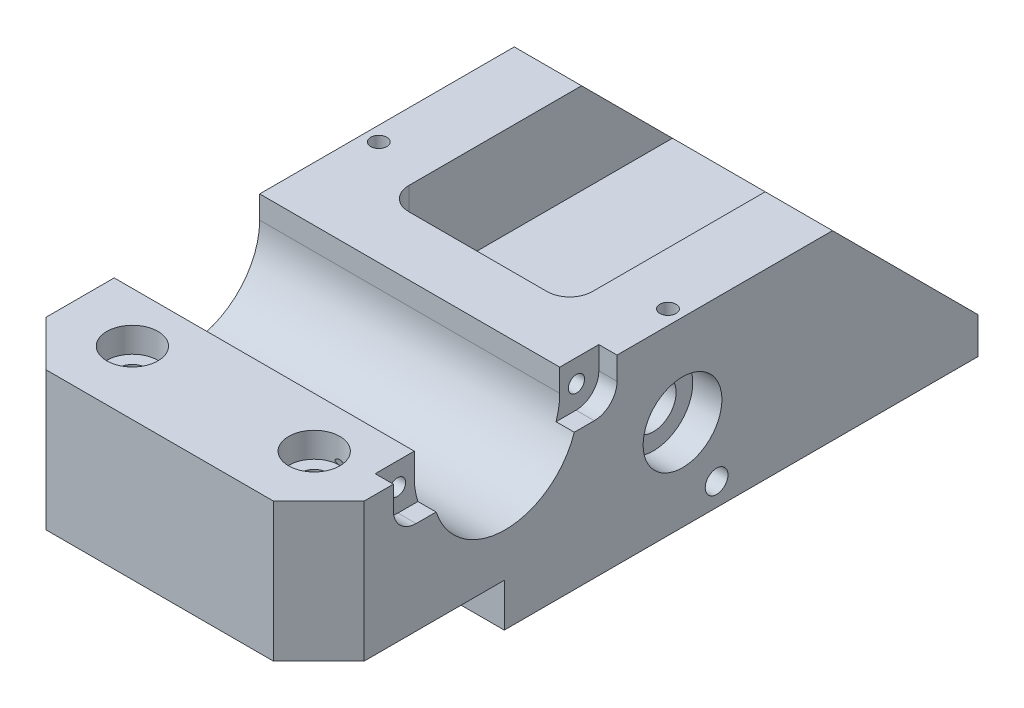
SolidWorks part; units mm, degrees
material "Nylon 6/10"
ref_plane "Front Plane" through (0, 0, 0) normal (0, 0, 1) x (1, 0, 0)
ref_plane "Top Plane" through (0, 0, 0) normal (0, 1, 0) x (1, 0, 0)
ref_plane "Right Plane" through (0, 0, 0) normal (1, 0, 0) x (0, 0, -1)
sketch "Sketch1" plane through (0, 0, 0) normal (0, 1, 0) x (1, 0, 0)
  line L1 (-22.225, -46.0375) -> (22.225, -46.0375)
  line L2 (-22.225, -46.0375) -> (-22.225, 46.0375)
  line L3 (-22.225, 46.0375) -> (22.225, 46.0375)
  line L4 (22.225, -46.0375) -> (22.225, 46.0375)
  line L5 (-22.225, -46.0375) -> (22.225, 46.0375) construction
  line L6 (-22.225, 46.0375) -> (22.225, -46.0375) construction
  point P0 (0, 0)
  dimension "D1" = 44.45
  dimension "D2" = 92.075
extrude "Base" add sketch "Sketch1" along normal blind 12.7 and the other way blind 12.7
sketch "Sketch2" plane through (0, 0, -46.0375) normal (0, 0, -1) x (-1, 0, 0)
  line L1 (-22.225, -12.7) -> (22.225, -12.7) construction
  circle A0 centre (0, -12.7) radius 4.7625
  dimension "D1" = 9.525
extrude "ShaftGuide" cut sketch "Sketch2" against normal blind 41.275
ref_plane "Plane1" through (0, -12.7, 0) normal (0, -1, 0) x (-1, 0, 0)
sketch "Sketch3" plane through (0, -12.7, 0) normal (0, -1, 0) x (-1, 0, 0)
  line L0 (10.922, -20.1295) -> (16.002, -20.1295)
  line L1 (22.225, -46.0375) -> (-22.225, -46.0375) construction
  line L2 (-22.225, -46.0375) -> (-22.225, 46.0375) construction
  line L3 (0, 0) -> (0, 102.0916) construction
  line L5 (-10.922, -20.1295) -> (-10.922, -3.3655)
  line L6 (-22.225, -46.0375) -> (22.225, -46.0375)
  line L7 (-10.922, -3.3655) -> (10.922, -3.3655)
  line L8 (10.922, -20.1295) -> (10.922, -3.3655)
  line L10 (-10.922, -20.1295) -> (-22.225, -20.1295)
  line L11 (-22.225, -46.0375) -> (-22.225, -20.1295)
  line L13 (22.225, -46.0375) -> (22.225, -20.1295)
  line L14 (4.7625, 46.0375) -> (4.7625, 4.7625)
  line L15 (4.7625, 4.7625) -> (-4.7625, 4.7625)
  line L16 (-4.7625, 4.7625) -> (-4.7625, 46.0375)
  line L17 (-4.7625, 46.0375) -> (-22.225, 46.0375)
  line L18 (-22.225, 46.0375) -> (-22.225, -46.0375)
  line L19 (-22.225, -46.0375) -> (22.225, -46.0375)
  line L20 (22.225, -46.0375) -> (22.225, 46.0375)
  line L21 (22.225, 46.0375) -> (4.7625, 46.0375)
  line L23 (22.225, 46.0375) -> (22.225, -46.0375) construction
  line L25 (-4.7625, 46.0375) -> (-22.225, 46.0375) construction
  line L26 (22.225, -20.1295) -> (16.002, -20.1295)
  line L28 (22.225, -46.0375) -> (22.225, 46.0375) construction
  line L29 (22.225, 46.0375) -> (4.7625, 46.0375) construction
  dimension "D6" = 21.844
  dimension "D3" = 49.403
  dimension "D7" = 16.764
  dimension "D1" = 0
extrude "ActuatorPlaneCut" cut sketch "Sketch3" against normal blind 6.0325
sketch "Sketch5" plane through (0, 0, 0) normal (0, 1, 0) x (1, 0, 0)
  line L1 (12.827, 11.1125) -> (-12.827, 11.1125)
  line L2 (12.827, -1.5875) -> (12.827, 11.1125)
  line L3 (12.827, -1.5875) -> (-12.827, -1.5875)
  line L4 (0, 0) -> (0, 121.8983) construction
  line L5 (-10.922, -3.3655) -> (10.922, -3.3655) construction
  line L6 (-12.827, -1.5875) -> (-12.827, 11.1125)
  point P17 (12.827, -1.5875)
  point P20 (12.827, 11.1125)
  dimension "D3" = 1.778
  dimension "D1" = 12.7
  dimension "D2" = 25.654
extrude "CenterSlot" cut sketch "Sketch5" along normal through all and the other way through all
fillet "CenterSlotFillet" radius 3.175 4 edges at (-12.827, 0, -11.1125) (-12.827, 0, 1.5875) (12.827, 0, 1.5875) (12.827, 0, -11.1125)
sketch "Sketch40" plane through (0, -12.7, 0) normal (0, -1, 0) x (1, 0, 0)
  line L1 (10.922, -0.9525) -> (-10.922, -0.9525)
  line L2 (10.922, -0.9525) -> (10.922, 16.9545)
  line L3 (7.747, 20.1295) -> (-7.747, 20.1295)
  line L4 (-10.922, -0.9525) -> (-10.922, 16.9545)
  line L6 (10.922, 3.3655) -> (10.922, 20.1295) construction
  line L7 (-9.652, 1.5875) -> (9.652, 1.5875) construction
  arc A0 (-7.747, 20.1295) -> (-10.922, 16.9545) centre (-7.747, 16.9545) ccw
  arc A1 (7.747, 20.1295) -> (10.922, 16.9545) centre (7.747, 16.9545) cw
  point P8 (-10.922, 20.1295)
  dimension "D1" = 3.175
  dimension "D2" = 2.54
extrude "GearBoxPit" cut sketch "Sketch40" against normal blind 11.176
sketch "Sketch60" plane through (0, 12.7, 0) normal (0, 1, 0) x (1, 0, 0)
  line L0 (22.225, 46.0375) -> (-22.225, 46.0375) construction
  line L1 (-12.827, 7.9375) -> (12.827, 7.9375)
  line L2 (-12.827, 7.9375) -> (-12.827, 46.0375)
  line L3 (-12.827, 46.0375) -> (12.827, 46.0375)
  line L4 (12.827, 7.9375) -> (12.827, 46.0375)
  line L5 (12.827, 1.5875) -> (12.827, 7.9375) construction
extrude "FrontCutaway" cut sketch "Sketch60" against normal blind 12.7
chamfer "ChamferFront" distance 20.32 angle 45 2 edges at (-17.526, 12.7, -46.0375) (17.526, 12.7, -46.0375)
sketch "Sketch67" plane through (0, -12.7, 0) normal (0, -1, 0) x (-1, 0, 0)
  line L0 (-12.3825, -5.3975) -> (12.3825, -5.3975) construction
  line L1 (-12.3825, -5.0006) -> (12.3825, -5.0006)
  line L2 (-12.3825, -5.7944) -> (12.3825, -5.7944)
  line L3 (-12.3825, -16.0655) -> (12.3825, -16.0655) construction
  line L4 (-12.3825, -15.6686) -> (12.3825, -15.6686)
  line L5 (-12.3825, -16.4624) -> (12.3825, -16.4624)
  line L6 (9.652, -1.5875) -> (-9.652, -1.5875) construction
  line L7 (0, 0.0055) -> (0, 0.7987) construction
  arc A0 (-12.3825, -5.0006) -> (-12.3825, -5.7944) centre (-12.3825, -5.3975) ccw
  arc A1 (12.3825, -5.7944) -> (12.3825, -5.0006) centre (12.3825, -5.3975) ccw
  arc A2 (-12.3825, -15.6686) -> (-12.3825, -16.4624) centre (-12.3825, -16.0655) ccw
  arc A3 (12.3825, -16.4624) -> (12.3825, -15.6686) centre (12.3825, -16.0655) ccw
  point P2 (0, -5.3975)
  point P9 (0, -16.0655)
  dimension "D1" = 0.7937
  dimension "D2" = 3.81
  dimension "D3" = 24.765
  dimension "D4" = 10.668
extrude "GearBoxSlotsH" cut sketch "Sketch67" against normal blind 2.286
sketch "Sketch55" plane through (-22.225, 0, 0) normal (-1, 0, 0) x (0, 0, 1)
  line L0 (-46.0375, -12.7) -> (20.1295, -12.7) construction
  line L1 (-11.1125, -12.7) -> (-11.1125, -7.9375) construction
  circle A0 centre (-9.525, -9.525) radius 1.5875
  dimension "D1" = 3.175
  dimension "D2" = 3.175
extrude "GuideBarHole" cut sketch "Sketch55" against normal through all
sketch "Sketch56" plane through (0, 0, 0) normal (1, 0, 0) x (0, 0, -1)
  line L0 (7.9375, -12.7) -> (1.5875, -12.7) construction
  line L1 (7.9375, -12.7) -> (1.5875, -12.7) construction
  line L2 (4.7625, -12.7) -> (4.7625, 12.7) construction
  line L3 (25.7175, 12.7) -> (-46.0375, 12.7) construction
  circle A0 centre (4.7625, 0) radius 3.175
  dimension "D1" = 6.35
extrude "PitchShaftHole" cut sketch "Sketch56" against normal through all and the other way through all
sketch "Sketch57" plane through (-22.225, 0, 0) normal (-1, 0, 0) x (0, 0, 1)
  circle A0 centre (-4.7625, 0) radius 5.5
  circle A1 centre (-4.7625, 0) radius 3.175 construction
  dimension "D1" = 11
extrude "BearingBoreR" cut sketch "Sketch57" against normal blind 4.064
mirror "BearingBoreL" about plane through (0, 0, 0) normal (1, 0, 0) of "BearingBoreR"
hole_wizard "BearingBoreSetScrews" positions "Sketch59" profile "Sketch58" tap size "#4-40" standard "ANSI Inch" end condition up to next
sketch "Sketch59" plane through (4.3433, 12.7, -10.3044) normal (0, 1, 0) x (1, 0, 0)
  line L5 (-26.5683, -0.0419) -> (-26.5683, -11.0419) construction
  line L6 (-26.5683, -0.0419) -> (-26.5683, -11.0419) construction
  line L7 (-26.5683, -5.5419) -> (17.8817, -5.5419) construction
  line L8 (17.8817, -56.3419) -> (17.8817, 15.4131) construction
  line L10 (-26.5683, 15.4131) -> (-26.5683, -56.3419) construction
  point P0 (-24.5363, -5.5419)
  point P2 (15.8497, -5.5419)
  dimension "D1" = 2.032
  dimension "D2" = 2.032
sketch "Sketch58" plane through (-20.193, 12.7, -4.7625) normal (1, 0, 0) x (0, 0, 1)
  line L0 (0, 0) -> (0, 7.2)
  line L1 (0, 7.2) -> (1.1303, 7.2)
  line L2 (1.1303, 7.2) -> (1.1303, 0)
  line L5 (1.1303, 0) -> (0, 0)
  line L11 (0, -6.35) -> (0, 107.95) construction
  dimension "Thru Tap Drill Dia." = 2.2606
  dimension "Thru Tap Drill Depth" = 7.2
cosmetic thread "Hole Thread18" parameters "D2"=2.8448
cosmetic thread "Hole Thread19" parameters "D2"=2.8448
hole_wizard "ToggleAssemHoles" positions "Sketch50" profile "Sketch49" tap size "#6-32" standard "ANSI Inch"
sketch "Sketch50" plane through (0, -12.7, 0) normal (0, -1, 0) x (-1, 0, 0)
  line L1 (4.7625, 46.0375) -> (-4.7625, 46.0375) construction
  line L2 (0, 0) -> (0, 49.3678) construction
  line L3 (-9.652, 11.1125) -> (-4.7625, 11.1125) construction
  point P0 (12.7, 23.8125)
  point P2 (-12.7, 23.8125)
  point P8 (0, 46.0375)
  dimension "D1" = 12.7
  dimension "D2" = 12.7
sketch "Sketch49" plane through (-12.7, -12.7, -23.8125) normal (1, 0, 0) x (0, 0, -1)
  line L0 (0, 0) -> (0, 10.2107)
  line L1 (0, 10.2107) -> (1.3525, 9.398)
  line L2 (1.3525, 9.398) -> (1.3525, 0)
  line L5 (1.3525, 0) -> (0, 0)
  line L10 (0, 10.2107) -> (-1.3526, 9.398) construction
  line L11 (0, -6.35) -> (0, 107.95) construction
  dimension "Tap Drill Dia." = 2.7051
  dimension "Tap Drill Depth" = 9.398
  dimension "Drill Angle" = 118
cosmetic thread "Hole Thread12" parameters "D1"=9.398, "D2"=3.5052
cosmetic thread "Hole Thread13" parameters "D1"=9.398, "D2"=3.5052
chamfer "BackChamfers" distance 6.35 angle 45 2 edges at (22.225, 3.0162, 46.0375) (-22.225, 3.0162, 46.0375)
sketch "Sketch62" plane through (-22.225, 0, 0) normal (-1, 0, 0) x (0, 0, 1)
  line L0 (-46.0375, -12.7) -> (-46.0375, -7.62) construction
  line L1 (-25.7175, 12.7) -> (39.6875, 12.7) construction
  line L2 (9.8425, 9.525) -> (9.8425, 12.7)
  line L3 (30.1625, 9.525) -> (30.1625, 12.7)
  line L4 (30.1625, 12.7) -> (9.8425, 12.7)
  arc A0 (9.8425, 9.525) -> (30.1625, 9.525) centre (20.0025, 9.525) ccw
  dimension "D1" = 20.32
  dimension "D2" = 66.04
  dimension "D3" = 3.175
extrude "PitchMotorSlot" cut sketch "Sketch62" against normal through all
sketch "Sketch63" plane through (22.225, 0, 0) normal (-1, 0, 0) x (0, 0, 1)
  line L1 (4.3815, 12.7) -> (35.6235, 12.7)
  line L2 (4.3815, 12.7) -> (4.3815, 9.525)
  line L3 (7.5565, 6.35) -> (32.4485, 6.35)
  line L4 (35.6235, 12.7) -> (35.6235, 9.525)
  line L5 (30.1625, 12.7) -> (9.8425, 12.7) construction
  arc A0 (32.4485, 6.35) -> (35.6235, 9.525) centre (32.4485, 9.525) ccw
  arc A1 (7.5565, 6.35) -> (4.3815, 9.525) centre (7.5565, 9.525) cw
  point P4 (20.0025, 12.7)
  dimension "D3" = 3.175
  dimension "D1" = 31.242
  dimension "D2" = 6.35
extrude "PitchMotorMountingSlots" cut sketch "Sketch63" along normal blind 2.54
hole_wizard "PitchMotorMountingHoles" positions "Sketch65" profile "Sketch64" tap size "#4-40" standard "ANSI Inch"
sketch "Sketch65" plane through (19.685, 0, 0) normal (1, 0, 0) x (0, 0, -1)
  line L0 (-35.6235, 12.7) -> (-30.1625, 12.7) construction
  line L3 (-30.1625, 12.7) -> (-9.8425, 12.7) construction
  line L5 (-20.0025, 12.7) -> (-20.0025, 7.4827) construction
  point P0 (-32.4993, 9.525)
  point P2 (-7.5057, 9.525)
  dimension "D1" = 3.175
  dimension "D2" = 24.9936
sketch "Sketch64" plane through (19.685, 9.525, 32.4993) normal (0, 1, 0) x (0, 0, -1)
  line L0 (0, 0) -> (0, 8.2738)
  line L1 (0, 8.2738) -> (1.1303, 7.5946)
  line L2 (1.1303, 7.5946) -> (1.1303, 0)
  line L5 (1.1303, 0) -> (0, 0)
  line L10 (0, 8.2738) -> (-1.1303, 7.5946) construction
  line L11 (0, -6.35) -> (0, 107.95) construction
  dimension "Tap Drill Dia." = 2.2606
  dimension "Tap Drill Depth" = 7.5946
  dimension "Drill Angle" = 118
cosmetic thread "Hole Thread20" parameters "D1"=7.5946, "D2"=2.8448
cosmetic thread "Hole Thread21" parameters "D1"=7.5946, "D2"=2.8448
hole_wizard "GearBoxMountingHoles" positions "Sketch69" profile "Sketch68" tap size "#6-32" standard "ANSI Inch"
sketch "Sketch69" plane through (0, -12.7, 0) normal (0, -1, 0) x (-1, 0, 0)
  line L0 (-12.3825, -5.7944) -> (-10.922, -5.7944) construction
  line L1 (-10.922, -15.6686) -> (-12.3825, -15.6686) construction
  line L2 (-22.225, -5.7944) -> (-10.922, -5.7944) construction
  line L3 (-10.922, -15.6686) -> (-22.225, -15.6686) construction
  line L4 (-16.5735, -15.6686) -> (-16.5735, -5.7944) construction
  line L6 (0, 0) -> (0, 15.1935) construction
  line L9 (-22.225, -20.1295) -> (-22.225, 46.0375) construction
  line L10 (10.922, -5.7944) -> (22.225, -5.7944) construction
  line L11 (22.225, 46.0375) -> (22.225, -20.1295) construction
  line L13 (10.922, -15.6686) -> (22.225, -15.6686) construction
  line L14 (12.3825, -15.6686) -> (10.922, -15.6686) construction
  line L15 (10.922, -15.6686) -> (10.922, -5.7944) construction
  line L17 (16.5735, -15.6686) -> (16.5735, -5.7944) construction
  point P0 (-16.5735, -10.7315)
  point P2 (16.5735, -10.7315)
sketch "Sketch68" plane through (16.5735, -12.7, 10.7315) normal (1, 0, 0) x (0, 0, -1)
  line L0 (0, 0) -> (0, 10.2107)
  line L1 (0, 10.2107) -> (1.3525, 9.398)
  line L2 (1.3525, 9.398) -> (1.3525, 0)
  line L5 (1.3525, 0) -> (0, 0)
  line L10 (0, 10.2107) -> (-1.3526, 9.398) construction
  line L11 (0, -6.35) -> (0, 107.95) construction
  dimension "Tap Drill Dia." = 2.7051
  dimension "Tap Drill Depth" = 9.398
  dimension "Drill Angle" = 118
hole_wizard "CapMountingHoles" positions "Sketch74" profile "Sketch73" counterbore size "#6" standard "ANSI Inch" end condition through all
sketch "Sketch74" plane through (-0.8379, 12.7, 8.6337) normal (0, -1, 0) x (-1, 0, 0)
  line L8 (-0.8379, -1002.5128) -> (-0.8379, 48997.4872) construction
  line L9 (15.0371, -37.4038) -> (-16.7129, -37.4038) construction
  point P0 (-13.5379, -28.5138)
  point P2 (11.8621, -28.5138)
  dimension "D1" = 25.4
  dimension "D2" = 8.89
sketch "Sketch73" plane through (12.7, 12.7, 37.1475) normal (1, 0, 0) x (0, 0, 1)
  line L0 (0, 0) -> (0, 25.4)
  line L1 (0, 25.4) -> (1.8288, 25.4)
  line L3 (1.8288, 25.4) -> (1.8288, 3.5052)
  line L4 (1.8288, 3.5052) -> (3.5725, 3.5052)
  line L5 (3.5725, 3.5052) -> (3.5725, 0)
  line L7 (3.5725, 0) -> (0, 0)
  line L11 (0, -6.35) -> (0, 107.95) construction
  dimension "Thru Hole Dia." = 3.6576
  dimension "Thru Hole Depth" = 25.4
  dimension "C'Bore Dia." = 7.145
  dimension "C'Bore Depth" = 3.5052
